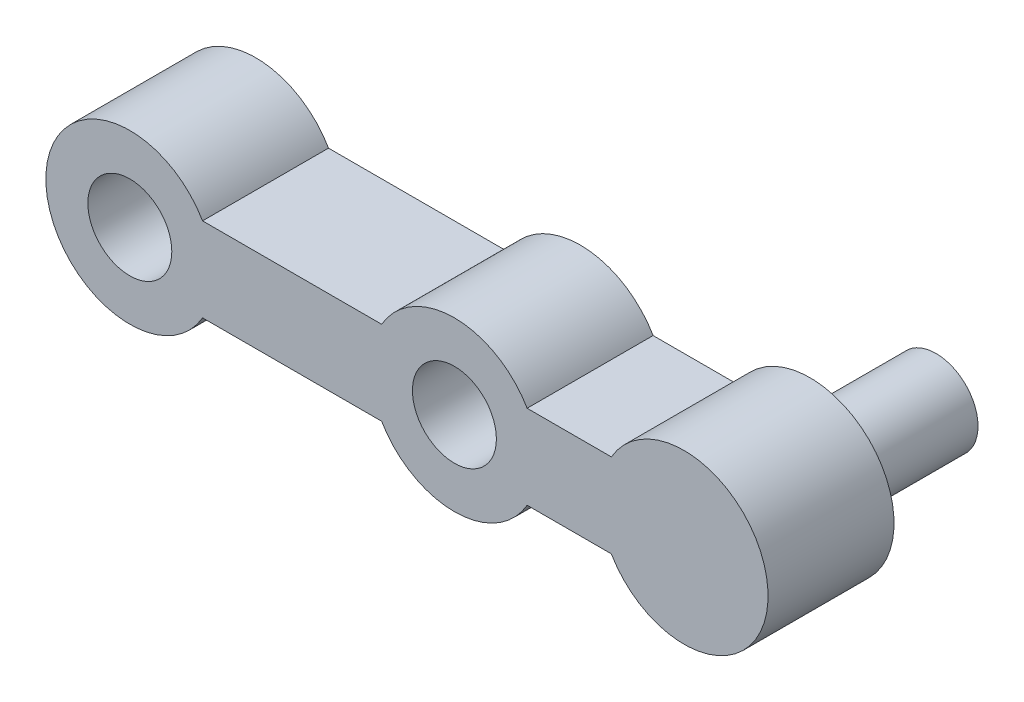
SolidWorks part; units mm, degrees
ref_plane "Спереди" through (0, 0, 0) normal (0, 0, 1) x (1, 0, 0)
ref_plane "Сверху" through (0, 0, 0) normal (0, 1, 0) x (1, 0, 0)
ref_plane "Справа" through (0, 0, 0) normal (1, 0, 0) x (0, 0, -1)
other "Configuration Table"
sketch "Sketch2" plane through (0, 0, 0) normal (0, 0, 1) x (1, 0, 0)
  line L0 (-17.3789, -4.8227) -> (-13.113, -4.8227)
  line L1 (-9.6489, -4.8227) -> (-7.643, -4.8227)
  line L3 (-38.8078, -5.8227) -> (10.4516, -5.8227) construction
  line L5 (-9.6489, -6.8227) -> (-7.643, -6.8227)
  line L6 (-17.3789, -6.8227) -> (-13.113, -6.8227)
  arc A3 (-17.3789, -4.8227) -> (-17.3789, -6.8227) centre (-19.1109, -5.8227) ccw
  arc A4 (-13.113, -6.8227) -> (-9.6489, -6.8227) centre (-11.3809, -5.8227) ccw
  arc A5 (-7.643, -6.8227) -> (-7.643, -4.8227) centre (-5.9109, -5.8227) ccw
  arc A6 (-17.1109, -5.8227) -> (-17.3789, -4.8227) centre (-19.1109, -5.8227) ccw construction
  arc A7 (-17.3789, -6.8227) -> (-17.1109, -5.8227) centre (-19.1109, -5.8227) ccw construction
  arc A8 (-13.3809, -5.8227) -> (-13.113, -6.8227) centre (-11.3809, -5.8227) ccw construction
  arc A9 (-13.113, -4.8227) -> (-13.3809, -5.8227) centre (-11.3809, -5.8227) ccw construction
  arc A10 (-9.6489, -6.8227) -> (-9.3809, -5.8227) centre (-11.3809, -5.8227) ccw construction
  arc A11 (-9.6489, -4.8227) -> (-13.113, -4.8227) centre (-11.3809, -5.8227) ccw
  arc A12 (-9.3809, -5.8227) -> (-9.6489, -4.8227) centre (-11.3809, -5.8227) ccw construction
  arc A13 (-7.643, -4.8227) -> (-7.9109, -5.8227) centre (-5.9109, -5.8227) ccw construction
  arc A14 (-7.9109, -5.8227) -> (-7.643, -6.8227) centre (-5.9109, -5.8227) ccw construction
  dimension "D4" = 4
  dimension "D1" = 7.73
  dimension "D2" = 5.47
  dimension "D3" = 2
extrude "Boss-Extrude1" add sketch "Sketch2" along normal blind 3 contours L1 A11 L0 A3 L6 A4 L5 A5 region at (-12.3971, -5.8227, 0)
ref_plane "Plane1" through (0, 0, 3) normal (0, 0, 1) x (1, 0, 0)
sketch "Sketch3" plane through (0, 0, 3) normal (0, 0, 1) x (1, 0, 0)
  circle A0 centre (-11.3809, -5.8227) radius 1
  circle A1 centre (-19.1109, -5.8227) radius 1
  dimension "D1" = 2
extrude "Cut-Extrude1" cut sketch "Sketch3" against normal up to surface (3 mm away) contours A0 | A1 region at (-11.3809, -5.8227, 3) up to face at (-11.9459, -5.8227, 0)
ref_plane "Plane2" through (0, 0, 0) normal (0, 0, -1) x (-1, 0, 0)
sketch "Sketch4" plane through (0, 0, 0) normal (0, 0, -1) x (-1, 0, 0)
  circle A0 centre (5.9109, -5.8227) radius 1
  circle A2 centre (11.3809, -5.8227) radius 1 construction
extrude "Boss-Extrude2" add sketch "Sketch4" along normal blind 3 contours A0
equation "\"R small\"= 2"
equation "\"R big\"= 4"
equation "\"width\"= 0.6"
equation "\"border width\"= 1"
equation "\"D4@Sketch2\"=\"R big\""
equation "\"D3@Sketch2\"=\"R small\""
equation "\"D1@Sketch3\"=\"R small\""
